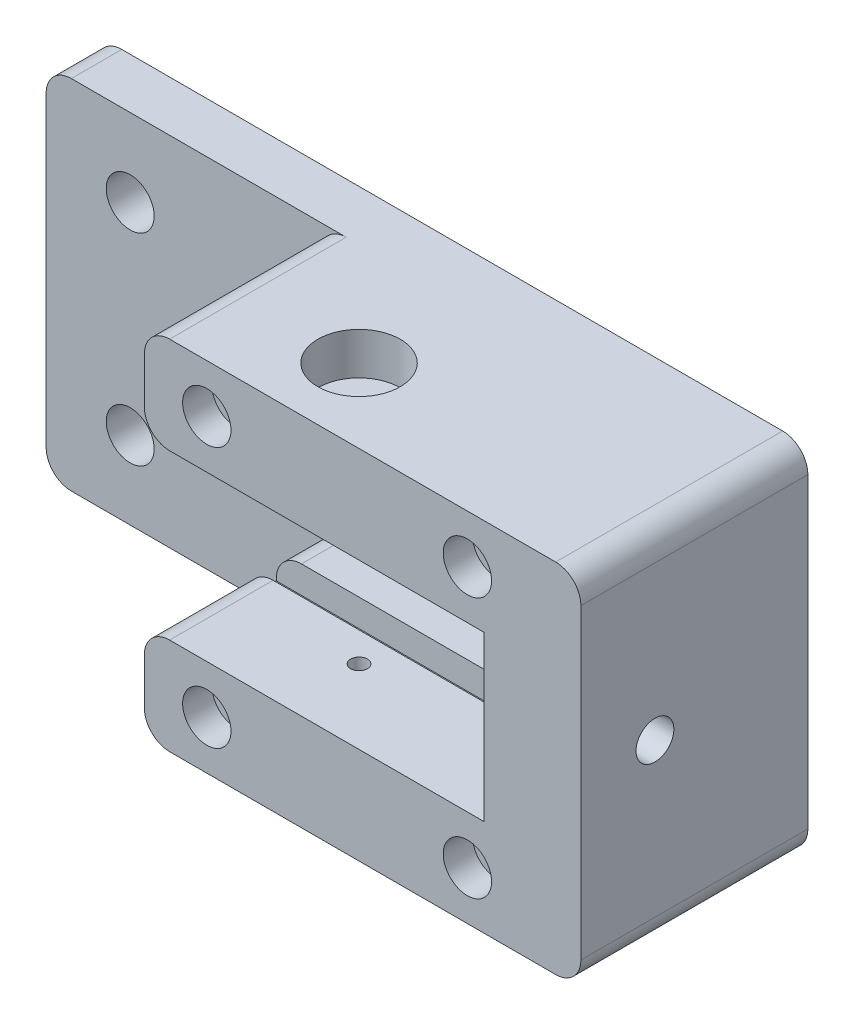
SolidWorks part; units mm, degrees
ref_plane "Front Plane" through (0, 0, 0) normal (0, 0, 1) x (1, 0, 0)
ref_plane "Top Plane" through (0, 0, 0) normal (0, 1, 0) x (1, 0, 0)
ref_plane "Right Plane" through (0, 0, 0) normal (1, 0, 0) x (0, 0, -1)
sketch "Sketch1" plane through (0, 0, 0) normal (0, 0, 1) x (1, 0, 0)
  line L0 (-44.7279, 20.3017) -> (33.883, 20.3017)
  line L1 (36.883, 17.3017) -> (36.883, -19.1983)
  line L2 (33.883, -22.1983) -> (-44.7279, -22.1983)
  line L3 (-47.7279, -19.1983) -> (-47.7279, 17.3017)
  line L4 (-37.7279, 20.3017) -> (-37.7279, -22.1983) construction
  line L5 (-47.7279, -0.9483) -> (36.883, -0.9483) construction
  line L6 (-47.7279, -12.9483) -> (36.883, -12.9483) construction
  line L7 (-47.7279, 11.0517) -> (36.883, 11.0517) construction
  line L8 (-7.617, 14.5517) -> (23.383, 14.5517) construction
  line L9 (23.383, 14.5517) -> (23.383, -0.9483) construction
  line L10 (-7.617, -16.4483) -> (23.383, -16.4483) construction
  line L11 (-7.617, 14.5517) -> (-7.617, -16.4483) construction
  line L12 (23.383, -0.9483) -> (23.383, -16.4483) construction
  line L14 (-44.7279, -22.1983) -> (-44.3476, -22.1323)
  arc A0 (33.883, 20.3017) -> (36.883, 17.3017) centre (33.883, 17.3017) cw
  arc A1 (36.883, -19.1983) -> (33.883, -22.1983) centre (33.883, -19.1983) cw
  arc A2 (-44.7279, -22.1983) -> (-47.7279, -19.1983) centre (-44.7279, -19.1983) cw
  arc A3 (-47.7279, 17.3017) -> (-44.7279, 20.3017) centre (-44.7279, 17.3017) cw
  circle A4 centre (-37.7279, 11.0517) radius 2.85
  circle A5 centre (-37.7279, -12.9483) radius 2.85
  circle A6 centre (-7.617, 14.5517) radius 1.725
  circle A7 centre (-7.617, -16.4483) radius 1.725
  circle A8 centre (23.383, -16.4483) radius 1.725
  circle A9 centre (23.383, 14.5517) radius 1.725
  dimension "D1" = 3
  dimension "D5" = 31
  dimension "D9" = 3.45
  dimension "D2" = 10
  dimension "D3" = 12
  dimension "D4" = 12
  dimension "D6" = 31
  dimension "D7" = 13.5
  dimension "D8" = 42.5
extrude "Boss-Extrude1" add sketch "Sketch1" along normal blind 6 contours A3 L3 A2 L2 A1 L1 A0 L0 A9 A8 A5 A4 A6 A7 region at (-5.0935, -0.9483, 0)
sketch "Sketch7" plane through (0, 0, 0) normal (0, 0, -1) x (-1, 0, 0)
  line L0 (-23.383, 14.5517) -> (7.617, -16.4483) construction
  circle A0 centre (-7.883, -0.9483) radius 11.125
extrude "Cut-Extrude4" cut sketch "Sketch7" against normal blind 2.5
sketch "Sketch8" plane through (0, 0, 0) normal (0, 0, -1) x (-1, 0, 0)
  circle A0 centre (-7.883, -0.9483) radius 7.5
  dimension "D1" = 15
extrude "Cut-Extrude5" cut sketch "Sketch8" against normal blind 6
sketch "Sketch10" plane through (0, 0, 6) normal (0, 0, 1) x (1, 0, 0)
  line L0 (-12.0393, 20.3017) -> (33.883, 20.3017)
  line L1 (-44.7279, 20.3017) -> (33.883, 20.3017) construction
  line L4 (-15.0393, 17.3017) -> (-15.0393, 11.8017)
  line L5 (33.883, -22.1983) -> (-44.7279, -22.1983) construction
  line L6 (-12.0393, -22.1983) -> (33.883, -22.1983)
  line L7 (36.883, 17.3017) -> (36.883, -19.1983)
  line L8 (-12.0393, 8.8017) -> (25.383, 8.8017)
  line L9 (25.383, 8.8017) -> (25.383, -10.6983)
  line L10 (25.383, -10.6983) -> (-12.0393, -10.6983)
  line L11 (-15.0393, -13.6983) -> (-15.0393, -19.1983)
  line L12 (36.883, -0.9483) -> (-15.1014, -0.9483) construction
  line L13 (1.6719, 8.8017) -> (1.6719, -0.9483) construction
  line L14 (1.6719, -0.9483) -> (1.6719, -10.6983) construction
  arc A2 (-12.0393, -22.1983) -> (-15.0393, -19.1983) centre (-12.0393, -19.1983) cw
  arc A3 (-12.0393, 20.3017) -> (-15.0393, 17.3017) centre (-12.0393, 17.3017) ccw
  arc A4 (36.883, -19.1983) -> (33.883, -22.1983) centre (33.883, -19.1983) cw
  arc A5 (36.883, 17.3017) -> (33.883, 20.3017) centre (33.883, 17.3017) ccw
  arc A6 (-15.0393, 11.8017) -> (-12.0393, 8.8017) centre (-12.0393, 11.8017) ccw
  arc A7 (-15.0393, -13.6983) -> (-12.0393, -10.6983) centre (-12.0393, -13.6983) cw
  circle A12 centre (-7.617, 14.5517) radius 1.725
  circle A13 centre (23.383, 14.5517) radius 1.725
  circle A14 centre (-7.617, -16.4483) radius 1.725
  circle A15 centre (23.383, -16.4483) radius 1.725
  point P13 (-15.0393, -22.1983)
  point P19 (-15.0393, 20.3017)
  point P30 (-15.0393, -10.6983)
  dimension "D1" = 3
  dimension "D2" = 3
  dimension "D6" = 3.45
  dimension "D4" = 11.5
  dimension "D5" = 11.5
extrude "Boss-Extrude4" add sketch "Sketch10" along normal blind 21
sketch "Sketch11" plane through (-15.0393, 0, 0) normal (-1, 0, 0) x (0, 0, 1)
  line L0 (11.31, 12.0517) -> (11.31, -13.9483)
  line L1 (11.31, -13.9483) -> (14.69, -13.9483)
  line L3 (6, -0.9483) -> (27, -0.9483) construction
  line L4 (6, 17.3017) -> (6, 11.8017) construction
  line L5 (13, -13.9483) -> (13, 12.0517) construction
  line L6 (11.31, -0.9483) -> (13, -0.9483) construction
  line L7 (13, -0.9483) -> (14.69, -0.9483) construction
  line L8 (11.31, 12.0517) -> (14.69, 12.0517)
  line L9 (6, 8.8017) -> (6, -10.6983) construction
  line L10 (27, 8.8017) -> (27, -10.6983) construction
  line L11 (13, 12.0517) -> (13, -0.9483) construction
  line L12 (13, -0.9483) -> (13, -13.9483) construction
  line L13 (14.69, 12.0517) -> (14.69, -13.9483)
  dimension "D1" = 7
  dimension "D2" = 3.38
  dimension "D3" = 26
extrude "Cut-Extrude6" cut sketch "Sketch11" against normal up to vertex (40.4223 mm away) up to point (25.383, 8.8017, 27)
sketch "Sketch14" plane through (0, 20.3017, 0) normal (0, 1, 0) x (1, 0, 0)
  line L0 (33.883, -27) -> (-12.0393, -27) construction
  line L5 (36.883, -27) -> (36.883, 0) construction
  circle A0 centre (1.683, -18.19) radius 1
  point P4 (36.883, -13.5)
  dimension "D1" = 8.81
  dimension "D3" = 2
  dimension "D2" = 35.2
extrude "Cut-Extrude7" cut sketch "Sketch14" against normal through all
chamfer "Chamfer1" distance 3 angle 45 1 edges at (1.683, -22.1983, 17.19)
sketch "Sketch19" plane through (0, 20.3017, 0) normal (0, 1, 0) x (1, 0, 0)
  circle A0 centre (1.683, -18.19) radius 4.9
  circle A1 centre (1.683, -18.19) radius 1
  dimension "D1" = 9.8
extrude "Cut-Extrude9" cut sketch "Sketch19" against normal blind 5
sketch "Sketch20" plane through (0, 15.3017, 0) normal (0, 1, 0) x (1, 0, 0)
  circle A0 centre (1.683, -18.19) radius 2.125
  dimension "D1" = 4.25
extrude "Cut-Extrude10" cut sketch "Sketch20" against normal blind 3
sketch "Sketch21" plane through (0, 0, 27) normal (0, 0, 1) x (1, 0, 0)
  circle A0 centre (23.383, 14.5517) radius 2.875
  circle A1 centre (23.383, -16.4483) radius 2.875
  circle A2 centre (-7.617, -16.4483) radius 2.875
  circle A3 centre (-7.617, 14.5517) radius 2.875
  dimension "D1" = 5.75
extrude "Cut-Extrude11" cut sketch "Sketch21" against normal blind 3.5
sketch "Sketch22" plane through (25.383, 0, 0) normal (-1, 0, 0) x (0, 0, 1)
  line L0 (11.31, 11.5517) -> (11.31, -13.9483)
  circle A0 centre (18.19, -0.9483) radius 2.25
  dimension "D1" = 4.5
  dimension "D2" = 6.88
extrude "Cut-Extrude12" cut sketch "Sketch22" against normal through all contours A0 region at (25.383, -0.9483, 18.19)
chamfer "Chamfer5" distance 3 angle 45 1 edges at (1.683, 8.8017, 19.19)
